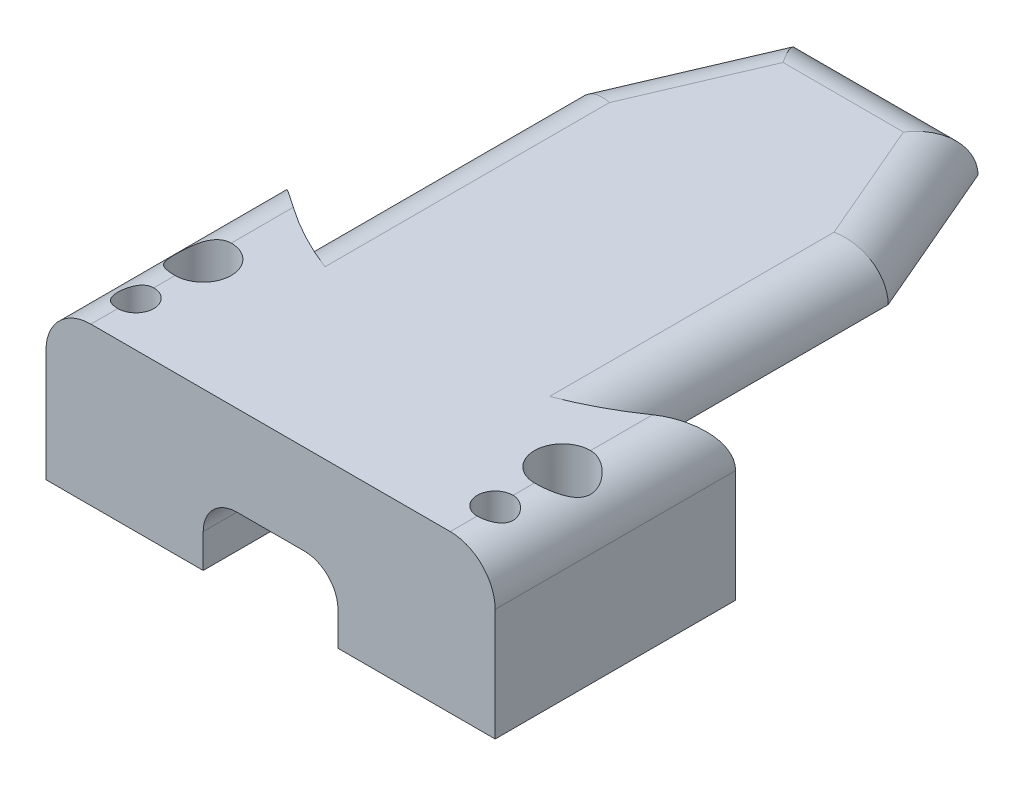
SolidWorks part; units mm, degrees
ref_plane "Front" through (0, 0, 0) normal (0, 0, 1) x (1, 0, 0)
ref_plane "Top" through (0, 0, 0) normal (0, 1, 0) x (1, 0, 0)
ref_plane "Right" through (0, 0, 0) normal (1, 0, 0) x (0, 0, -1)
sketch "Sketch5" plane through (0, 0, 0) normal (0, 1, 0) x (1, 0, 0)
  line L0 (0, 0) -> (0, 14) construction
  line L1 (-10, -6.5) -> (10, -6.5)
  line L2 (-10, -6.5) -> (-10, 4.202)
  line L6 (10, -6.5) -> (10, 4.202)
  arc A0 (-10, 4.202) -> (10, 4.202) centre (0, 14) ccw
extrude "Boss-Extrude1" add sketch "Sketch5" against normal blind 7
sketch "Sketch6" plane through (0, 0, 0) normal (0, 1, 0) x (1, 0, 0)
  line L0 (0, 0) -> (0, 14) construction
  line L1 (-7, 14) -> (-7, 0)
  line L2 (-7, 0) -> (7, 0)
  line L3 (7, 0) -> (7, 14)
  line L4 (0, 21) -> (4, 21)
  line L5 (0, 21) -> (-4, 21)
  line L6 (-4, 21) -> (-7, 14)
  line L7 (4, 21) -> (7, 14)
extrude "Boss-Extrude2" add sketch "Sketch6" against normal blind 2
sketch "Sketch3" plane through (0, 0, 0) normal (0, 0, 1) x (1, 0, 0)
  line L9 (0, -7) -> (0, -5.5) construction
  line L13 (0, -7) -> (-3, -7)
  line L16 (0, -5.5) -> (1.5, -5.5) construction
  line L17 (0, -5.5) -> (-1.5, -5.5) construction
  line L18 (-3, -7) -> (-3, -5.5)
  line L19 (0, -7) -> (3, -7)
  line L20 (3, -7) -> (3, -5.5)
  line L21 (-1.5, -4) -> (1.5, -4)
  arc A2 (-3, -5.5) -> (-1.5, -4) centre (-1.5, -5.5) cw
  arc A3 (3, -5.5) -> (1.5, -4) centre (1.5, -5.5) ccw
extrude "Cut-Extrude1" cut sketch "Sketch3" against normal through all from offset 6.5 contours L20 A3 L21 A2 L18 L13 L19 region at (0, -5.566, 0)
fillet "Fillet1" radius 2 7 edges at (10, 0, 1.149) (-10, 0, 1.149) (7, 0, -7.9378) (-7, 0, -7.9378) (0, 0, -21) (-5.5, 0, -17.5) (5.5, 0, -17.5)
sketch "Sketch2" plane through (0, 0, 0) normal (0, 1, 0) x (1, 0, 0)
  line L0 (0, 0) -> (0, -1.5) construction
  line L2 (0, -1.5) -> (-8, -1.5) construction
  line L3 (0, -1.5) -> (8, -1.5) construction
  line L5 (0, -1.5) -> (0, -4.5) construction
  line L6 (0, -4.5) -> (-8, -4.5) construction
  line L7 (0, -4.5) -> (8, -4.5) construction
  circle A0 centre (-8, -1.5) radius 0.8
  circle A1 centre (8, -1.5) radius 0.8
  circle A2 centre (8, -4.5) radius 0.8
  circle A3 centre (-8, -4.5) radius 0.8
extrude "Screw Holes" cut sketch "Sketch2" against normal through all
sketch "Sketch4" plane through (0, 0, 0) normal (0, 1, 0) x (1, 0, 0)
  circle A2 centre (-8, -1.5) radius 1.25
  circle A3 centre (8, -1.5) radius 1.25
extrude "Screw Heads" cut sketch "Sketch4" against normal blind 3
